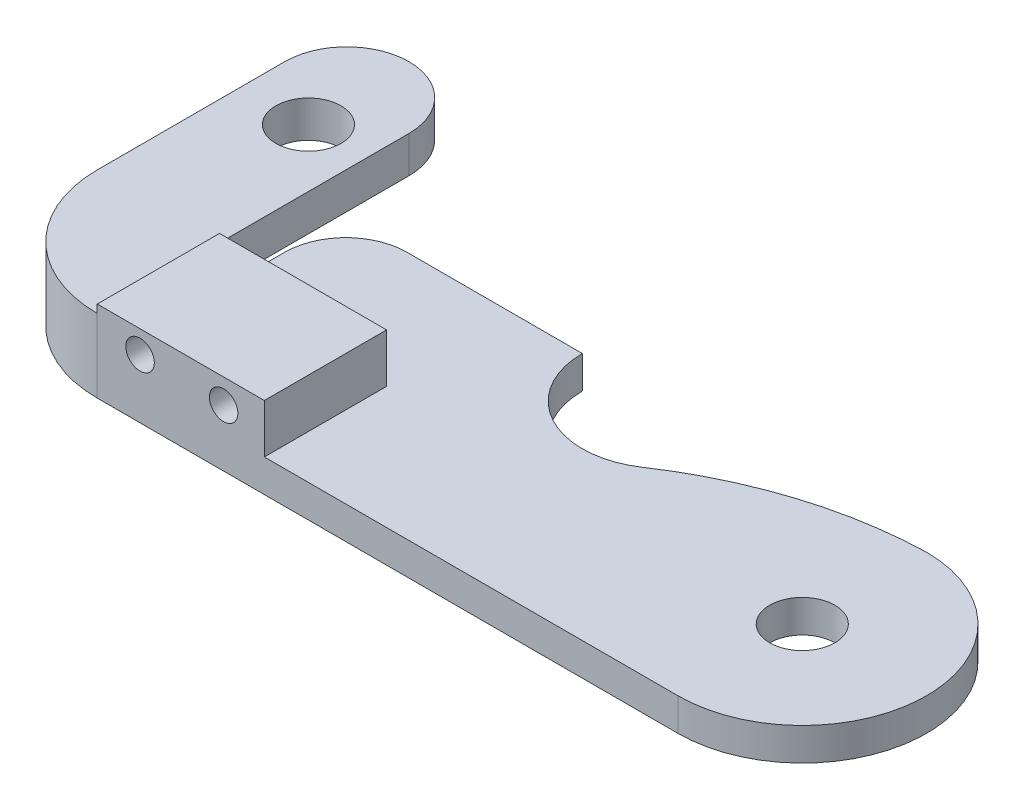
SolidWorks part; units mm, degrees
ref_plane "Front Plane" through (0, 0, 0) normal (0, 0, 1) x (1, 0, 0)
ref_plane "Top Plane" through (0, 0, 0) normal (0, 1, 0) x (1, 0, 0)
ref_plane "Right Plane" through (0, 0, 0) normal (1, 0, 0) x (0, 0, -1)
sketch "Sketch1" plane through (0, 0, 0) normal (0, 1, 0) x (1, 0, 0)
  line L0 (-13.6869, -1.9274) -> (14.8131, -1.9274)
  line L1 (14.8131, -1.9274) -> (14.8131, 4.1726) construction
  line L2 (14.8131, 10.2726) -> (6.0201, 10.2726)
  line L3 (-13.6869, 7.2726) -> (-13.6869, 4.1726)
  line L4 (-2.0799, 10.2726) -> (-10.6869, 10.2726)
  line L5 (-13.6869, 4.1726) -> (-19.7869, 4.1726) construction
  line L6 (-13.6869, 4.1726) -> (-13.6869, -1.9274)
  arc A0 (14.8131, -1.9274) -> (14.8131, 10.2726) centre (14.8131, 4.1726) ccw
  circle A1 centre (14.8131, 4.1726) radius 1.6
  arc A2 (-10.6869, 10.2726) -> (-13.6869, 7.2726) centre (-10.6869, 7.2726) ccw
  arc A3 (-2.0799, 10.2726) -> (6.0201, 10.2726) centre (1.9701, 10.2726) ccw
  arc A4 (-19.7869, 4.1726) -> (-13.6869, -1.9274) centre (-13.6869, 4.1726) ccw construction
  dimension "D3" = 3.2
  dimension "D4" = 6
  dimension "D5" = 8.1
  dimension "D1" = 28.5
  dimension "D2" = 6.1
  dimension "D6" = 6.1
  dimension "D7" = 11.607
extrude "Boss-Extrude1" add sketch "Sketch1" along normal blind 1.6
sketch "Sketch2" plane through (0, 1.6, 0) normal (0, 1, 0) x (1, 0, 0)
  line L1 (-13.6869, -1.9274) -> (-5.4869, -1.9274)
  line L2 (-13.6869, -1.9274) -> (-13.6869, 4.0726)
  line L3 (-13.6869, 4.0726) -> (-5.4869, 4.0726)
  line L4 (-5.4869, -1.9274) -> (-5.4869, 4.0726)
  dimension "D1" = 8.2
  dimension "D2" = 6
extrude "Boss-Extrude2" add sketch "Sketch2" along normal blind 2.4
sketch "Sketch3" plane through (0, 0, 1.9274) normal (0, 0, 1) x (1, 0, 0)
  line L0 (-5.4869, 4) -> (-5.4869, 1.6) construction
  line L1 (-13.6869, 4) -> (-5.4869, 4) construction
  circle A0 centre (-11.5857, 2.9) radius 0.7
  circle A1 centre (-7.4869, 2.8) radius 0.7
  dimension "D1" = 1.4
  dimension "D2" = 1.4
  dimension "D3" = 2
  dimension "D4" = 4.1
  dimension "D5" = 1.2
extrude "Cut-Extrude1" cut sketch "Sketch3" against normal up to surface (6 mm away) up to face at (-9.5869, 2.8, -4.0726)
ref_plane "Plane1" through (0, 1.8, 0) normal (0, 1, 0) x (1, 0, 0)
sketch "Sketch4" plane through (0, 0, 0) normal (0, -1, 0) x (1, 0, 0)
  line L0 (-13.6869, 1.9274) -> (-13.6869, -4.1726)
  line L2 (-13.6869, -4.1726) -> (-19.7869, -4.1726)
  arc A0 (-13.6869, 1.9274) -> (-19.7869, -4.1726) centre (-13.6869, -4.1726) ccw
  dimension "D1" = 6.1
extrude "Boss-Extrude3" add sketch "Sketch4" against normal blind 3.6 separate body
sketch "Sketch5" plane through (0, 0, -4.1726) normal (0, 0, -1) x (-1, 0, 0)
  line L0 (19.7869, 3.6) -> (19.7869, 0) construction
  line L1 (13.6869, 3.6) -> (19.7869, 3.6)
  line L2 (13.6869, 3.6) -> (13.6869, 1.8)
  line L3 (13.6869, 1.8) -> (19.7869, 1.8)
  line L4 (19.7869, 3.6) -> (19.7869, 1.8)
  line L5 (2.0799, 1.6) -> (10.6869, 1.6) construction
  dimension "D1" = 0.2
extrude "Boss-Extrude4" add sketch "Sketch5" along normal blind 9.2
sketch "Sketch6" plane through (0, 3.6, 0) normal (0, 1, 0) x (1, 0, 0)
  line L0 (-19.7869, 13.3726) -> (-13.6869, 13.3726) construction
  line L1 (-19.7869, 13.3726) -> (-13.6869, 13.3726)
  arc A0 (-13.6869, 13.3726) -> (-19.7869, 13.3726) centre (-16.7369, 13.3726) ccw
extrude "Boss-Extrude5" add sketch "Sketch6" against normal up to surface (1.8 mm away) up to face at (-16.7369, 1.8, -8.7726)
sketch "Sketch7" plane through (0, 3.6, 0) normal (0, 1, 0) x (1, 0, 0)
  circle A0 centre (-16.53, 11.2801) radius 1.6
  circle A1 centre (-16.53, 11.2801) radius 1.6 construction
  dimension "D2" = 3.2
  dimension "D1" = 0
extrude "Cut-Extrude2" cut sketch "Sketch7" against normal up to surface (1.8 mm away) up to face at (-16.7369, 1.8, -9.5351)
fillet "Fillet1" radius 20 1 edges at (6.0201, 0.8, -10.2726)
